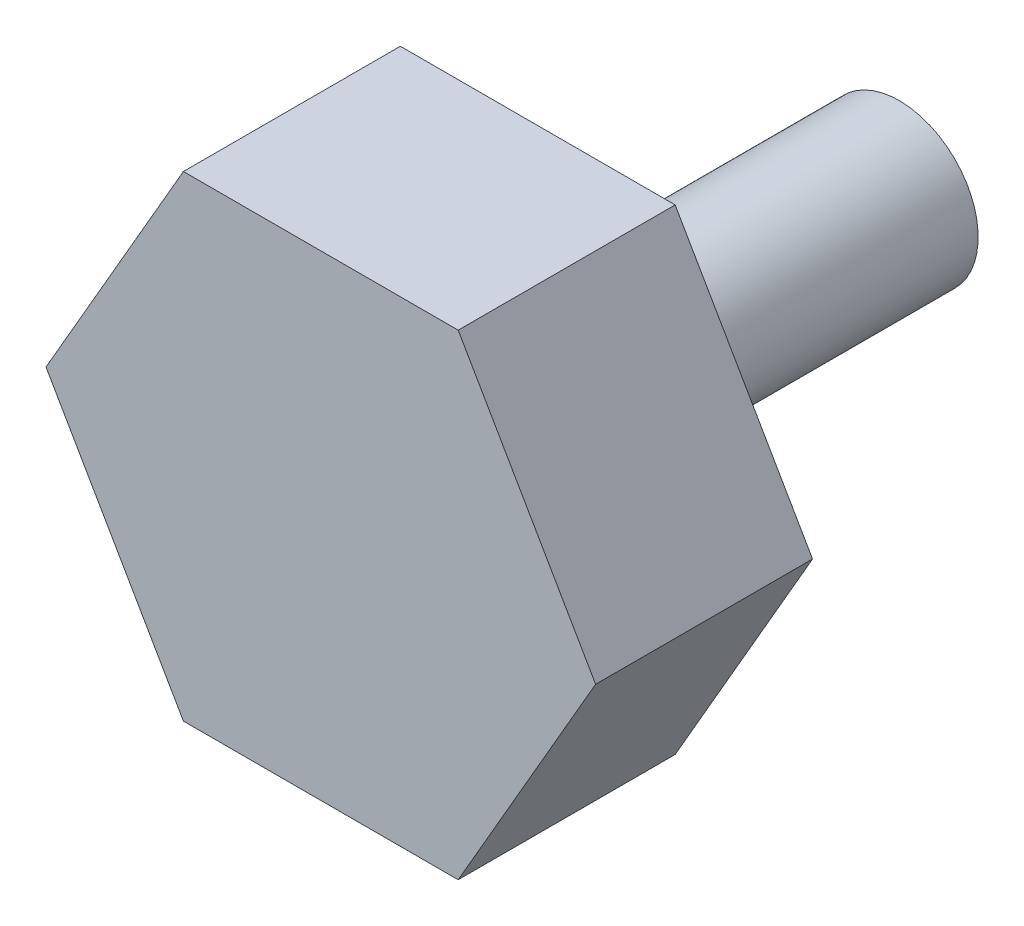
SolidWorks part; units mm, degrees
material "1100-H16 Rod (SS)"
ref_plane "Front Plane" through (0, 0, 0) normal (0, 0, 1) x (1, 0, 0)
ref_plane "Top Plane" through (0, 0, 0) normal (0, 1, 0) x (1, 0, 0)
ref_plane "Right Plane" through (0, 0, 0) normal (1, 0, 0) x (0, 0, -1)
sketch "Sketch1" plane through (0, 0, 0) normal (0, 0, 1) x (1, 0, 0)
  line L1 (1.9, -3.2909) -> (3.8, 0)
  line L2 (3.8, 0) -> (1.9, 3.2909)
  line L3 (1.9, 3.2909) -> (-1.9, 3.2909)
  line L4 (-1.9, 3.2909) -> (-3.8, 0)
  line L5 (-3.8, 0) -> (-1.9, -3.2909)
  line L6 (-1.9, -3.2909) -> (1.9, -3.2909)
  circle A0 centre (0, 0) radius 3.2909 construction
  dimension "D1" = 3.8
extrude "Boss-Extrude1" add sketch "Sketch1" along normal blind 3
sketch "Sketch2" plane through (0, 0, 0) normal (0, 0, -1) x (-1, 0, 0)
  circle A0 centre (0, 0) radius 1.09
  dimension "D1" = 2.18
extrude "Boss-Extrude2" add sketch "Sketch2" along normal blind 5
cosmetic thread "Cosmetic Thread1" parameters "D2"=1.18
cosmetic thread "Cosmetic Thread2" parameters "D2"=1.18
